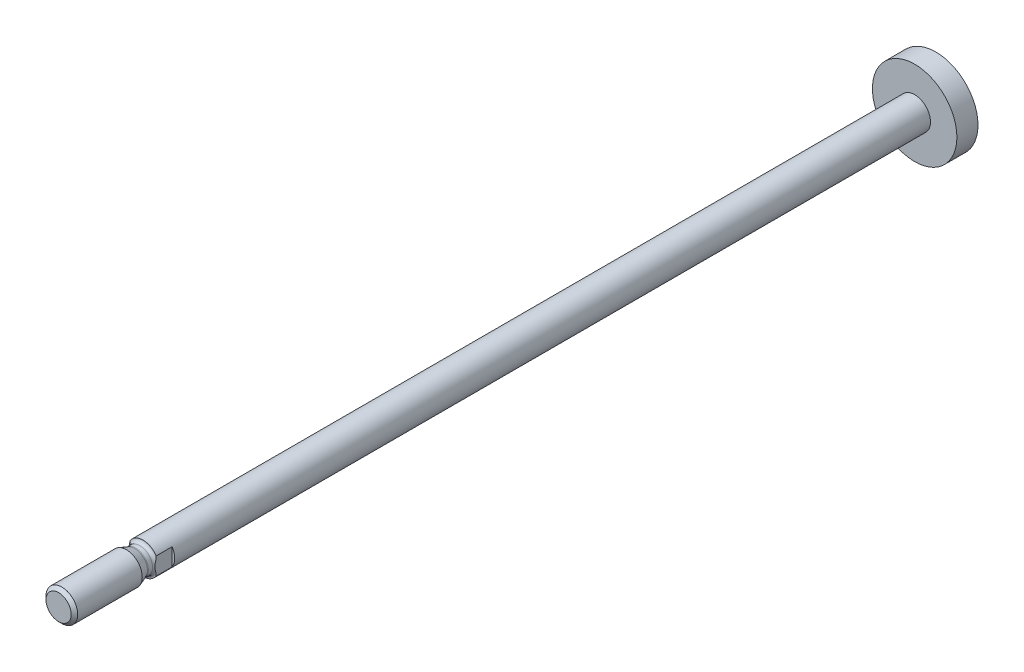
SolidWorks part; units mm, degrees
ref_plane "Front Plane" through (0, 0, 0) normal (0, 0, 1) x (1, 0, 0)
ref_plane "Top Plane" through (0, 0, 0) normal (0, 1, 0) x (1, 0, 0)
ref_plane "Right Plane" through (0, 0, 0) normal (1, 0, 0) x (0, 0, -1)
sketch "Sketch1" plane through (0, 0, 0) normal (1, 0, 0) x (0, 0, -1)
  line L0 (-5, 0) -> (-5, 3)
  line L1 (-5, 3) -> (141.2, 3)
  line L2 (141.2, 3) -> (141.2, 8)
  line L3 (141.2, 8) -> (145.2, 8)
  line L4 (145.2, 8) -> (145.2, 0)
  line L5 (145.2, 0) -> (-5, 0)
  line L6 (145.2, 0) -> (-5, 0) construction
revolve "Revolve1" add sketch "Sketch1" angle 360 about L6 reverse direction yes
sketch "Sketch2" plane through (0, 0, 0) normal (1, 0, 0) x (0, 0, -1)
  line L0 (-21, 0) -> (-21, 2.3865)
  line L1 (-21, 2.3865) -> (-20.3865, 3)
  line L2 (-20.3865, 3) -> (-8.1485, 3)
  line L3 (-8.1485, 3) -> (-6.5994, 2.4362)
  line L4 (-6.3942, 2.4) -> (-5.6, 2.4)
  line L5 (-5, 3) -> (-4, 3)
  line L6 (-4, 3) -> (-4, 0)
  line L7 (-4, 0) -> (-21, 0)
  line L8 (-4, 0) -> (-21, 0) construction
  arc A0 (-6.5994, 2.4362) -> (-6.3942, 2.4) centre (-6.3942, 3) ccw
  arc A1 (-5.6, 2.4) -> (-5, 3) centre (-5.6, 3) ccw
revolve "Revolve2" add sketch "Sketch2" angle 360 about L8 reverse direction yes
cosmetic thread "Cosmetic Thread1" parameters "D1"=12.8515, "D2"=4.773
ref_plane "Plane1" through (0, 0, 5) normal (0, 0, 1) x (1, 0, 0)
ref_plane "Plane2" through (0, 0, 2) normal (0, 0, 1) x (1, 0, 0)
sketch "Sketch3" plane through (0, 0, 2) normal (0, 0, 1) x (1, 0, 0)
  line L0 (-5, 10) -> (-5, -5)
  line L1 (-5, -5) -> (-2.5, -5)
  line L2 (-2.5, -5) -> (-2.5, 5)
  line L3 (-2.5, 5) -> (2.5, 5)
  line L4 (2.5, 5) -> (2.5, -5)
  line L5 (2.5, -5) -> (5, -5)
  line L6 (5, -5) -> (5, 10)
  line L7 (5, 10) -> (-5, 10)
extrude "Cut-Extrude1" cut sketch "Sketch3" along normal blind 4
ref_plane "Plane3" through (0, 0, -295) normal (0, 0, 1) x (1, 0, 0)
ref_plane "Plane4" through (0, 0, 16) normal (0, 0, 1) x (1, 0, 0)
ref_plane "Plane5" through (0, 0, 11.2) normal (0, 0, 1) x (1, 0, 0)
ref_plane "FDT_KSAUFSATZ XY" through (0, 0, 11.2) normal (0, 0, 1) x (1, 0, 0)
ref_plane "FDT_KSAUFSATZ XZ" through (0, 0, 0) normal (0, 1, 0) x (1, 0, 0)
ref_plane "FDT_KSAUFSATZ YZ" through (0, 0, 0) normal (-1, 0, 0) x (0, 0, 1)
ref_axis "FDT_KSAUFSATZ X" through (80.9, 0, 11.2) along (-1, 0, 0)
ref_axis "FDT_KSAUFSATZ Y" through (0, 50, 11.2) along (0, -1, 0)
ref_axis "FDT_KSAUFSATZ Z" through (0, 0, 80.9) along (0, 0, -1)
sketch3d "FDT_KSAUFSATZ"
  point P0 (0, 0, 11.2)
ref_plane "FDT_NUT XY" through (0, 0, 11.2) normal (0, 0, 1) x (1, 0, 0)
ref_plane "FDT_NUT XZ" through (0, 0, 0) normal (0, 1, 0) x (1, 0, 0)
ref_plane "FDT_NUT YZ" through (0, 0, 0) normal (-1, 0, 0) x (0, 0, 1)
ref_axis "FDT_NUT X" through (80.9, 0, 11.2) along (-1, 0, 0)
ref_axis "FDT_NUT Y" through (0, 50, 11.2) along (0, -1, 0)
ref_axis "FDT_NUT Z" through (0, 0, 80.9) along (0, 0, -1)
sketch3d "FDT_NUT"
  point P0 (0, 0, 11.2)
ref_plane "KS XY" through (0, 0, 0) normal (0, 0, -1) x (-1, 0, 0)
ref_plane "KS XZ" through (0, 0, 0) normal (0, 1, 0) x (1, 0, 0)
ref_plane "KS YZ" through (0, 0, 0) normal (1, 0, 0) x (0, 0, -1)
ref_axis "KS X" through (-80.9, 0, 0) along (1, 0, 0)
ref_axis "KS Y" through (0, 50, 0) along (0, -1, 0)
ref_axis "KS Z" through (0, 0, -80.9) along (0, 0, 1)
sketch3d "KS"
  point P0 (0, 0, 0)
ref_plane "NUT1 XY" through (0, 0, 16) normal (0, 0, 1) x (1, 0, 0)
ref_plane "NUT1 XZ" through (0, 0, 0) normal (0, -1, 0) x (-1, 0, 0)
ref_plane "NUT1 YZ" through (0, 0, 0) normal (1, 0, 0) x (0, 0, -1)
ref_axis "NUT1 X" through (-80.9, 0, 16) along (1, 0, 0)
ref_axis "NUT1 Y" through (0, -50, 16) along (0, 1, 0)
ref_axis "NUT1 Z" through (0, 0, 80.9) along (0, 0, -1)
sketch3d "NUT1"
  point P0 (0, 0, 16)
other "Freeze***"
